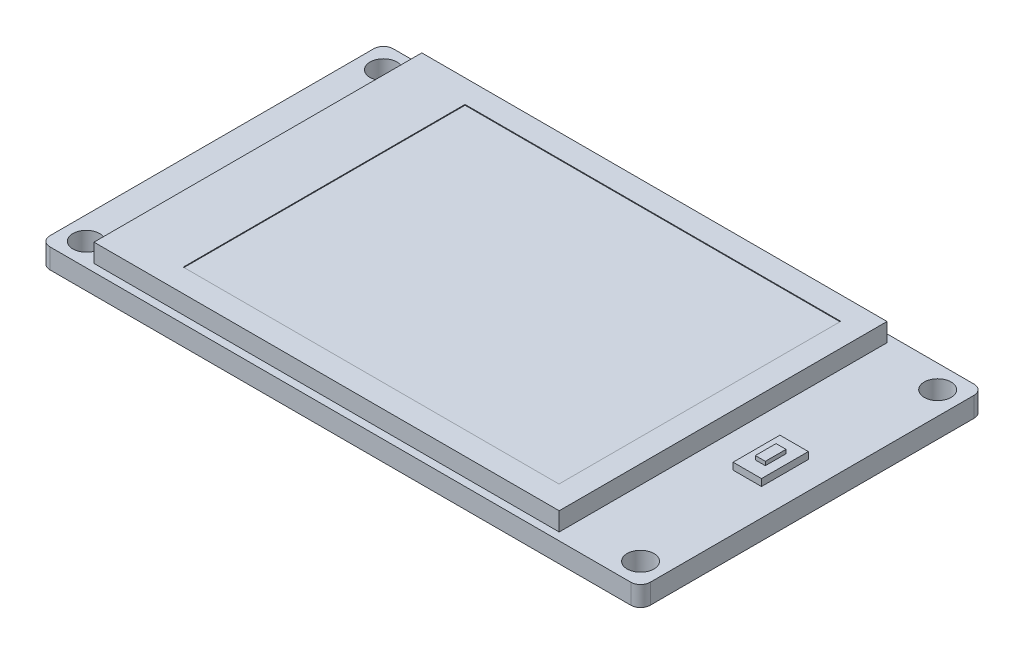
SolidWorks part; units mm, degrees
note: The reader was unsure of these and kept them because the rebuilt part matched: shared geometry of "草图1<3>", "草图1<4>", "草图1<5>", "草图1<6>", "草图1<7>".
ref_plane "前视基准面" through (0, 0, 0) normal (0, 0, 1) x (1, 0, 0)
ref_plane "上视基准面" through (0, 0, 0) normal (0, 1, 0) x (1, 0, 0)
ref_plane "右视基准面" through (0, 0, 0) normal (1, 0, 0) x (0, 0, -1)
sketch "草图1" plane through (0, 0, 0) normal (0, 1, 0) x (1, 0, 0)
  line L0 (-2.8, 0) -> (12.9721, 0) construction
  line L1 (-37.84, 22.36) -> (37.84, 22.36)
  line L2 (-39.11, 21.09) -> (-39.11, -21.09)
  line L3 (-37.84, -22.36) -> (37.84, -22.36)
  line L4 (39.11, 21.09) -> (39.11, -21.09)
  line L5 (-39.11, 22.36) -> (39.11, -22.36) construction
  line L6 (-39.11, -22.36) -> (39.11, 22.36) construction
  line L7 (12.9721, 0) -> (-2.8, 0) construction
  line L8 (0, 0) -> (0, 7.9751) construction
  line L9 (33.71, 0) -> (12.9721, 0) construction
  line L10 (-33.11, 21.36) -> (27.51, 21.36)
  line L11 (-33.11, 21.36) -> (-33.11, -21.36)
  line L12 (-33.11, -21.36) -> (27.51, -21.36)
  line L13 (27.51, 21.36) -> (27.51, -21.36)
  line L14 (-33.11, 21.36) -> (27.51, -21.36) construction
  line L15 (-33.11, -21.36) -> (27.51, 21.36) construction
  line L16 (31.86, -3.05) -> (35.56, -3.05)
  line L17 (31.86, -3.05) -> (31.86, 3.05)
  line L18 (31.86, 3.05) -> (35.56, 3.05)
  line L19 (35.56, -3.05) -> (35.56, 3.05)
  line L20 (31.86, -3.05) -> (35.56, 3.05) construction
  line L21 (31.86, 3.05) -> (35.56, -3.05) construction
  line L22 (33.06, -1.35) -> (34.36, -1.35)
  line L23 (33.06, -1.35) -> (33.06, 1.35)
  line L24 (33.06, 1.35) -> (34.36, 1.35)
  line L25 (34.36, -1.35) -> (34.36, 1.35)
  line L26 (33.06, -1.35) -> (34.36, 1.35) construction
  line L27 (33.06, 1.35) -> (34.36, -1.35) construction
  line L29 (-1.5, 21.36) -> (2.5, 21.36)
  line L36 (-24.48, -18.36) -> (24.48, -18.36)
  line L37 (-24.48, -18.36) -> (-24.48, 18.36)
  line L38 (-24.48, 18.36) -> (24.48, 18.36)
  line L39 (24.48, -18.36) -> (24.48, 18.36)
  circle A0 centre (-36.11, -19.36) radius 1.75
  arc A1 (-39.11, -21.09) -> (-37.84, -22.36) centre (-37.84, -21.09) ccw
  arc A2 (-37.84, 22.36) -> (-39.11, 21.09) centre (-37.84, 21.09) ccw
  arc A3 (37.84, 22.36) -> (39.11, 21.09) centre (37.84, 21.09) cw
  arc A4 (37.84, -22.36) -> (39.11, -21.09) centre (37.84, -21.09) ccw
  circle A5 centre (36.11, -19.36) radius 1.75
  circle A6 centre (-36.11, 19.36) radius 1.75
  circle A7 centre (36.11, 19.36) radius 1.75
  point P0 (0, 0)
  point P11 (33.71, 0)
  point P38 (33.71, 0)
  dimension "D5" = 3.5
  dimension "D6" = 42.72
  dimension "D7" = 60.62
  dimension "D1" = 44.72
  dimension "D2" = 78.22
  dimension "D3" = 3
  dimension "D4" = 3
  dimension "D8" = 48.96
  dimension "D9" = 36.72
  dimension "D10" = 3.03
  dimension "D11" = 6
  dimension "D12" = 6.1
  dimension "D13" = 3.7
  dimension "D14" = 2.7
  dimension "D15" = 1.3
  dimension "D16" = 3
  dimension "D17" = 5.4
extrude "凸台-拉伸1" add sketch "草图1" along normal blind 1.6
extrude "凸台-拉伸2" add sketch "草图1<3>" along normal blind 5 contours L13 L10 L11 L12 | L36 L39 L38 L37
sketch "草图1<3>" plane through (0, 0, 0) normal (0, 1, 0) x (1, 0, 0) same geometry as "草图1"
extrude "凸台-拉伸3" add sketch "草图1<4>" along normal blind 1 from offset 1.6
sketch "草图1<4>" plane through (0, 0, 0) normal (0, 1, 0) x (1, 0, 0) same geometry as "草图1"
extrude "切除-拉伸1" cut sketch "草图1<5>" against normal blind 0.1 from surface at 5 contours L36 L39 L38 L37 starting at face at (-2.8, 5, 0)
sketch "草图1<5>" plane through (0, 0, 0) normal (0, 1, 0) x (1, 0, 0) same geometry as "草图1"
extrude "凸台-拉伸4" add sketch "草图1<6>" along normal blind 3.5 contours L16 L19 L18 L17 L25 L22 L23 L24
sketch "草图1<6>" plane through (0, 0, 0) normal (0, 1, 0) x (1, 0, 0) same geometry as "草图1"
extrude "凸台-拉伸5" add sketch "草图1<7>" along normal blind 4 contours L22 L25 L24 L23
sketch "草图1<7>" plane through (0, 0, 0) normal (0, 1, 0) x (1, 0, 0) same geometry as "草图1"
sketch "草图2" plane through (0, 0, 0) normal (0, 1, 0) x (1, 0, 0)
  line L0 (-39.11, 21.09) -> (-39.11, -21.09) construction
  line L1 (-39.61, 13.14) -> (-39.11, 13.14)
  line L2 (-39.61, 13.14) -> (-39.61, -13.36)
  line L3 (-39.61, -13.36) -> (-39.11, -13.36)
  line L4 (-39.11, 13.14) -> (-39.11, -13.36)
  line L5 (-37.84, -22.36) -> (37.84, -22.36) construction
  dimension "D1" = 26.5
  dimension "D2" = 9
  dimension "D3" = 0.5
extrude "凸台-拉伸6" add sketch "草图2" against normal blind 2 separate body
